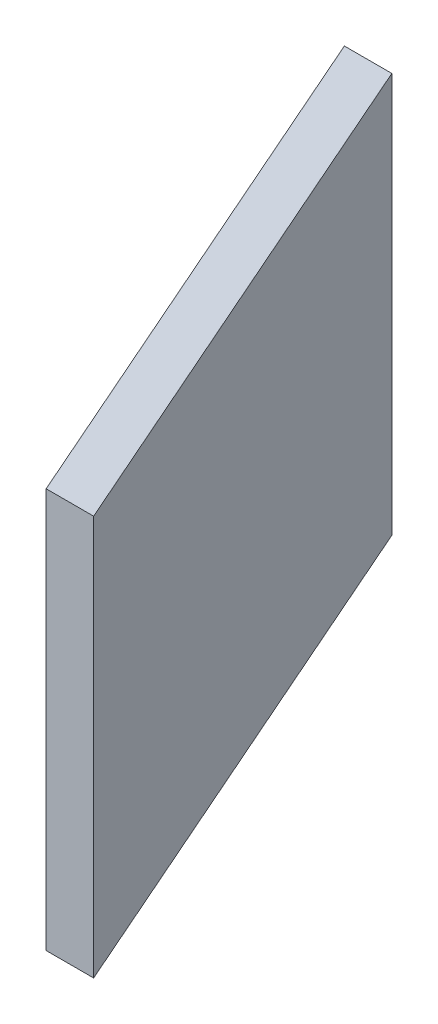
SolidWorks part; units mm, degrees
ref_plane "Front Plane" through (0, 0, 0) normal (0, 0, 1) x (1, 0, 0)
ref_plane "Top Plane" through (0, 0, 0) normal (0, 1, 0) x (1, 0, 0)
ref_plane "Right Plane" through (0, 0, 0) normal (1, 0, 0) x (0, 0, -1)
sketch "Sketch1" plane through (0, 0, 0) normal (0, 1, 0) x (1, 0, 0)
  line L0 (0, 0) -> (-10.7803, 24.5)
  line L1 (-10.7803, 24.5) -> (-8.5952, 24.5)
  line L2 (-8.5952, 24.5) -> (2.185, 0)
  line L3 (2.185, 0) -> (0, 0)
  dimension "D1" = 2
  dimension "D2" = 24.5
  dimension "D3" = 66.25
extrude "Boss-Extrude1" add sketch "Sketch1" along normal blind 18.4
